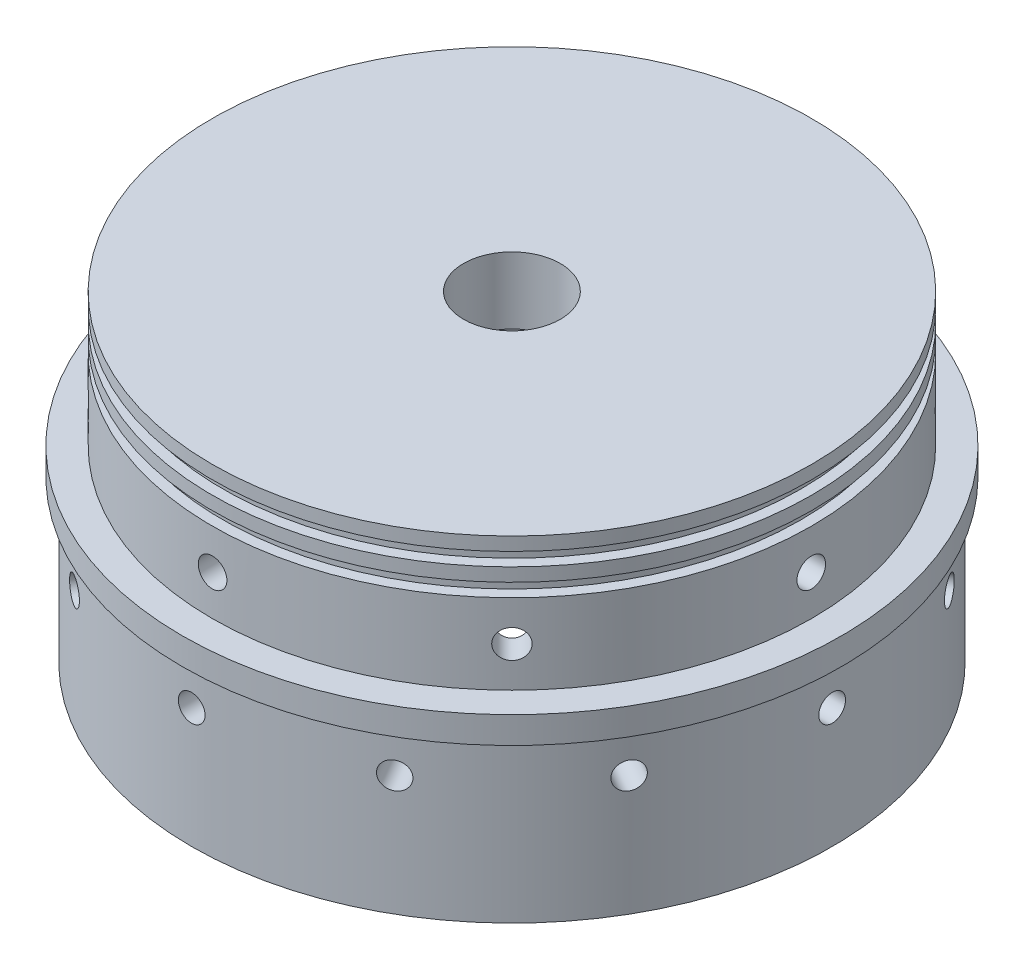
SolidWorks part; units mm, degrees
material "2024-T4"
ref_plane "Front Plane" through (0, 0, 0) normal (0, 0, 1) x (1, 0, 0)
ref_plane "Top Plane" through (0, 0, 0) normal (0, 1, 0) x (1, 0, 0)
ref_plane "Right Plane" through (0, 0, 0) normal (1, 0, 0) x (0, 0, -1)
sketch "Sketch1" plane through (0, 0, 0) normal (0, 1, 0) x (1, 0, 0)
  circle A0 centre (0, 0) radius 78.359
  dimension "D1" = 156.718
extrude "CenterRing(TotOD&Thk)" add sketch "Sketch1" along normal blind 6.35 contours A0 region at (0, 0, 0)
sketch "Sketch2" plane through (0, 6.35, 0) normal (0, 1, 0) x (1, 0, 0)
  circle A0 centre (0, 0) radius 71.247
  dimension "D1" = 142.494
extrude "TankRing(TankID&Ht)" add sketch "Sketch2" along normal blind 31.75
sketch "Sketch3" plane through (0, 0, 0) normal (0, -1, 0) x (1, 0, 0)
  circle A0 centre (0, 0) radius 76.2
  dimension "D1" = 152.4
extrude "FbrGlsRing(FbrGlsID&Ht)" add sketch "Sketch3" along normal blind 38.1
sketch "Sketch4" plane through (0, -38.1, 0) normal (0, -1, 0) x (1, 0, 0)
  circle A0 centre (0, 0) radius 65.0875
  circle A1 centre (0, 0) radius 76.2 construction
  circle A2 centre (0, 0) radius 76.2
  dimension "D1" = 130.175
extrude "Wall&BlkhdThk" cut sketch "Sketch4" against normal offset from surface (60.325 mm away) 15.875 contours A0 up to face at (0, 38.1, 71.247)
sketch "Sketch5" plane through (0, 0, 0) normal (0, 0, 1) x (1, 0, 0)
  line L0 (71.247, 38.1) -> (-71.247, 38.1) construction
  line L1 (-71.247, 38.1) -> (-71.247, 6.35) construction
  line L2 (-71.247, 38.1) -> (-71.247, 6.35)
  line L3 (71.247, 38.1) -> (-71.247, 38.1)
  line L4 (-71.247, 34.925) -> (-68.707, 34.925)
  line L5 (-68.707, 34.925) -> (-68.707, 31.75)
  line L6 (-68.707, 31.75) -> (-71.247, 31.75)
  line L7 (-71.247, 28.575) -> (-68.707, 28.575)
  line L8 (-68.707, 28.575) -> (-68.707, 25.4)
  line L9 (-68.707, 25.4) -> (-71.247, 25.4)
  line L10 (0, 6.35) -> (0, 38.1) construction
  line L11 (78.359, 6.35) -> (-78.359, 6.35) construction
  dimension "D1" = 2.54
  dimension "D2" = 3.175
  dimension "D3" = 3.175
  dimension "D4" = 3.175
  dimension "D5" = 3.175
revolve "O-Ring Channel" cut sketch "Sketch5" angle 360 about L10 region at (-69.977, 33.3375, 0) region at (-69.977, 26.9875, 0)
sketch "Sketch6" plane through (0, 0, 0) normal (0, 0, 1) x (1, 0, 0)
  line L0 (78.359, 6.35) -> (-78.359, 6.35) construction
  line L1 (78.359, 6.35) -> (-78.359, 6.35)
  circle A0 centre (0, 15.875) radius 3.4
  dimension "D1" = 6.8
  dimension "D2" = 9.525
extrude "TankBoltHole" cut sketch "Sketch6" against normal through all contours A0 region at (0, 15.875, 0)
pattern_circular "TankBoltCount" count 8 over 360 about axis through (0, 38.1, 0) along (0, -1, 0) of "TankBoltHole"
sketch "Sketch7" plane through (0, 0, 0) normal (0, 0, 1) x (1, 0, 0)
  line L0 (-76.2, 0) -> (76.2, 0) construction
  line L1 (-76.2, 0) -> (76.2, 0)
  circle A0 centre (0, -9.525) radius 3.175
  dimension "D1" = 6.35
  dimension "D2" = 9.525
extrude "FbrGlsBoltHole" cut sketch "Sketch7" against normal through all contours A0 region at (0, -9.525, 0)
pattern_circular "FbrGlsBoltCount" count 12 over 360 about axis through (0, -38.1, 0) along (0, 1, 0) of "FbrGlsBoltHole" reverse direction yes
sketch "Sketch8" plane through (0, 38.1, 0) normal (0, 1, 0) x (1, 0, 0)
  circle A0 centre (0, 0) radius 11.5094
  dimension "D1" = 23.0188
extrude "3/4NPTFemDrill" cut sketch "Sketch8" against normal through all
fillet "Smoothing" radius 12.7 1 edges at (0, 22.225, 65.0875)
sketch "Sketch9" plane through (0, -38.1, 0) normal (0, -1, 0) x (1, 0, 0)
  circle A0 centre (0, 0) radius 71.4375
  circle A1 centre (0, 0) radius 76.2 construction
  circle A2 centre (0, 0) radius 76.2
  dimension "D1" = 4.7625
extrude "FbrGlsRingTrim" cut sketch "Sketch9" against normal blind 19.05 contours A0
equation "\"D4@Sketch5\"=\"D2@Sketch5\""
equation "\"D5@Sketch5\"=\"D3@Sketch5\""
